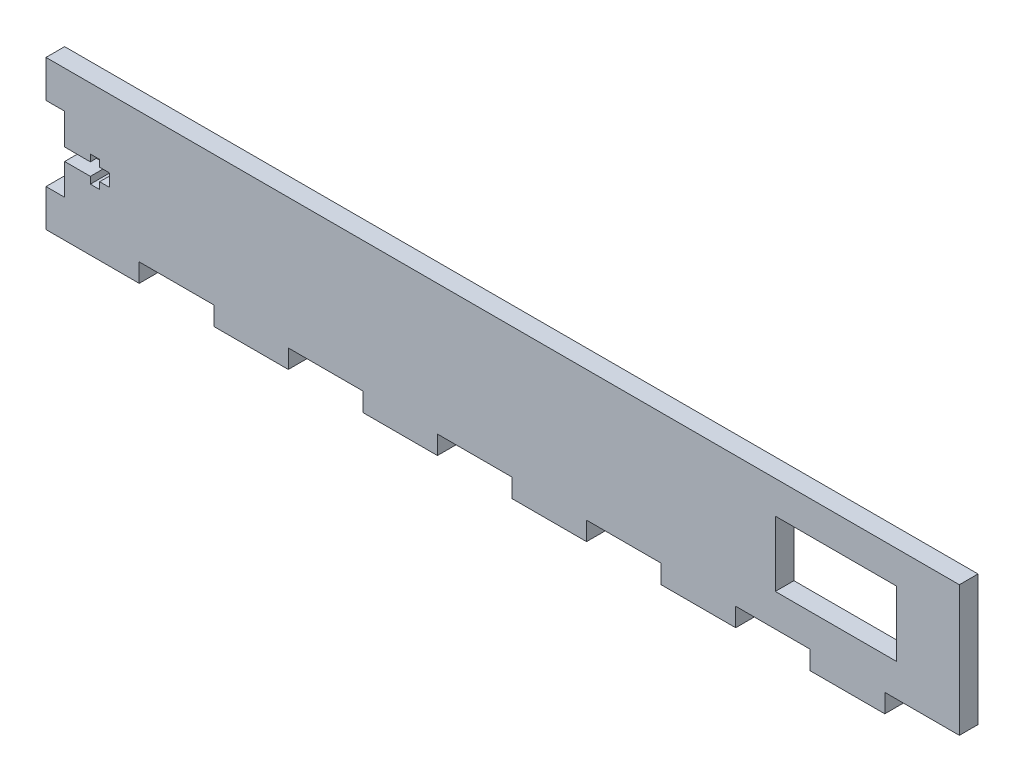
SolidWorks part; units mm, degrees
ref_plane "Front Plane" through (0, 0, 0) normal (0, 0, 1) x (1, 0, 0)
ref_plane "Top Plane" through (0, 0, 0) normal (0, 1, 0) x (1, 0, 0)
ref_plane "Right Plane" through (0, 0, 0) normal (1, 0, 0) x (0, 0, -1)
sketch "Sketch1" plane through (0, 0, 0) normal (0, 0, 1) x (1, 0, 0)
  line L0 (-262.733, -54.9538) -> (-262.733, 69.85) construction
  line L1 (42.067, 22.225) -> (-262.733, 22.225)
  line L2 (42.067, 22.225) -> (42.067, -22.225)
  line L3 (42.067, -22.225) -> (-262.733, -22.225)
  line L4 (-262.733, 22.225) -> (-262.733, -22.225)
  line L5 (63.0291, 0) -> (-62.7737, 0) construction
  line L6 (-19.6295, 10.033) -> (19.6295, 10.033) construction
  line L7 (19.6295, -10.033) -> (-19.6295, -10.033) construction
  line L8 (27.25, 6.27) -> (27.25, 8.0899) construction
  dimension "D1" = 44.45
  dimension "D2" = 14.817
extrude "Boss-Extrude1" add sketch "Sketch1" along normal blind 6.35
sketch "Sketch2" plane through (0, 0, 6.35) normal (0, 0, 1) x (1, 0, 0)
  line L0 (-41.9443, 0) -> (30.2812, 0) construction
  line L1 (-20.6375, 11.1125) -> (20.6375, 11.1125)
  line L2 (-20.6375, 11.1125) -> (-20.6375, -11.1125)
  line L3 (-20.6375, -11.1125) -> (20.6375, -11.1125)
  line L4 (20.6375, 11.1125) -> (20.6375, -11.1125)
  line L5 (-19.6295, 10.033) -> (19.6295, 10.033) construction
  line L6 (19.6295, -10.033) -> (-19.6295, -10.033) construction
  line L7 (0, 34.6052) -> (0, -28.4279) construction
  line L8 (-20.1295, -9.533) -> (-20.1295, 9.533) construction
  line L9 (20.1295, 9.533) -> (20.1295, -9.533) construction
  dimension "D1" = 22.225
  dimension "D2" = 41.275
extrude "Cut-Extrude1" cut sketch "Sketch2" against normal through all
ref_plane "Plane1" through (42.067, -22.225, 6.35) normal (1, 0, 0) x (0, 0, -1)
sketch "Sketch5" plane through (0, -22.225, 0) normal (0, -1, 0) x (1, 0, 0)
  line L0 (-262.733, 6.35) -> (42.067, 6.35) construction
  line L1 (16.667, 6.35) -> (-8.733, 6.35)
  line L2 (16.667, 6.35) -> (16.667, 0)
  line L3 (16.667, 0) -> (-8.733, 0)
  line L4 (-8.733, 6.35) -> (-8.733, 0)
  line L5 (-262.733, 0) -> (42.067, 0) construction
  dimension "D1" = 25.4
  dimension "D2" = 25.4
extrude "Boss-Extrude2" add sketch "Sketch5" along normal blind 6.35
pattern_linear "LPattern1" count 6 spacing 50.8 along (-1, 0, 0) of "Boss-Extrude2"
sketch "Sketch6" plane through (-262.733, 0, 0) normal (-1, 0, 0) x (0, 0, 1)
  line L0 (0, 22.225) -> (6.35, 22.225)
  line L1 (6.35, 22.225) -> (6.35, 9.525)
  line L2 (6.35, 22.225) -> (6.35, -28.575) construction
  line L3 (6.35, 9.525) -> (0, 9.525)
  line L4 (0, 22.225) -> (0, -28.575) construction
  line L5 (0, 9.525) -> (0, 22.225)
  dimension "D1" = 12.7
extrude "Boss-Extrude3" add sketch "Sketch6" along normal blind 6.35
pattern_linear "LPattern2" count 2 spacing 38.1 along (0, -1, 0) of "Boss-Extrude3"
sketch "Sketch7" plane through (0, 0, 6.35) normal (0, 0, 1) x (1, 0, 0)
  line L0 (-257.1687, -3.175) -> (-223.3079, -3.175) construction
  line L1 (-269.083, 9.525) -> (-262.733, 9.525) construction
  line L2 (-269.083, -15.875) -> (-262.733, -15.875) construction
  line L3 (-262.733, 9.525) -> (-262.733, -15.875) construction
  line B0 (-262.733, -1.0414) -> (-262.733, -5.3086)
  line B1 (-250.795, -5.3086) -> (-250.795, -7.62)
  line B2 (-250.795, -7.62) -> (-253.97, -7.62)
  line B3 (-253.97, -7.62) -> (-253.97, -5.3086)
  line B4 (-253.97, -5.3086) -> (-262.733, -5.3086)
  line B5 (-250.795, -5.3086) -> (-247.493, -5.3086)
  line B6 (-247.493, -5.3086) -> (-247.493, -1.0414)
  line B7 (-250.795, -1.0414) -> (-247.493, -1.0414)
  line B8 (-253.97, -1.0414) -> (-262.733, -1.0414)
  line B9 (-253.97, 1.27) -> (-253.97, -1.0414)
  line B10 (-250.795, 1.27) -> (-253.97, 1.27)
  line B11 (-250.795, -1.0414) -> (-250.795, 1.27)
sketch_block_instance "TSlot-1"
sketch_block "TSlot" parameters "D1"=3.302, "D2"=3.175
extrude "Cut-Extrude2" cut sketch "Sketch7" against normal through all
